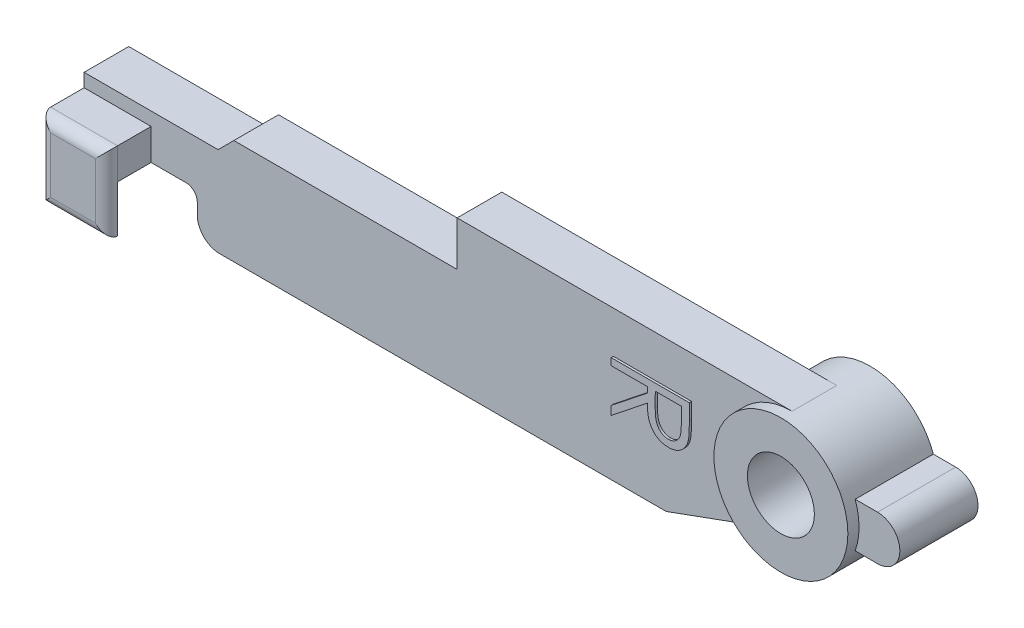
SolidWorks part; units mm, degrees
ref_plane "Piano frontale" through (0, 0, 0) normal (0, 0, 1) x (1, 0, 0)
ref_plane "Piano superiore" through (0, 0, 0) normal (0, 1, 0) x (1, 0, 0)
ref_plane "Piano destro" through (0, 0, 0) normal (1, 0, 0) x (0, 0, -1)
sketch "Schizzo1" plane through (0, 0, 0) normal (0, 0, 1) x (1, 0, 0)
  line L0 (19.0188, 0) -> (-19.0188, 0) construction
  line L1 (0, 0) -> (0, 8.6004) construction
  line L2 (-16.7071, 0.7929) -> (-10.7071, 0.7929)
  line L3 (-10.7071, 0.7929) -> (-10, 1.5)
  line L4 (-10, 1.5) -> (0, 1.5)
  line L5 (0, 1.5) -> (0, 3.5)
  line L6 (0, 3.5) -> (15, 3.5)
  line L7 (15, 3.5) -> (15, 0)
  line L8 (15, 0) -> (15, -1.155)
  line L9 (15, -1.155) -> (9.3618, -3.2071)
  line L10 (9.3618, -3.2071) -> (-11.6382, -3.2071)
  line L11 (-11.6382, -3.2071) -> (-11.6382, -1.2071)
  line L12 (-11.6382, -1.2071) -> (-16.7071, -1.2071)
  line L13 (-16.7071, -1.2071) -> (-16.7071, 0.7929)
  point P4 (0, 0)
  dimension "D1" = 15
  dimension "D2" = 10
  dimension "D3" = 6
  dimension "D4" = 1
  dimension "D5" = 2
  dimension "D6" = 6
  dimension "D7" = 20
  dimension "D8" = 21
  dimension "D9" = 3.5
  dimension "D10" = 45
  dimension "D11" = 2
  dimension "D12" = 2
extrude "Estrusione-Estrusione1" add sketch "Schizzo1" along normal blind 2
fillet "Raccordo1" radius 1 1 edges at (-11.6382, -3.2071, 1)
fillet "Raccordo2" radius 0.5 1 edges at (-11.6382, -1.2071, 1)
sketch "Schizzo2" plane through (0, 0, 0) normal (0, 0, 1) x (1, 0, 0)
  line L0 (-10.7071, 0.7929) -> (22.9117, 0.7929) construction
  line L1 (15, -1.155) -> (15, 3.5) construction
  line L2 (15, 3.5) -> (0, 3.5) construction
  circle A0 centre (15, 0.5) radius 3
  dimension "D1" = 6
extrude "Estrusione-Estrusione2" add sketch "Schizzo2" along direction (0, 0, -1) on the side of the normal blind 2.5 and the other way blind 1.5
sketch "Schizzo3" plane through (0, 0, 0) normal (0, 0, 1) x (1, 0, 0)
  line L0 (15, 0.5) -> (16.6892, 0.5) construction
  line L1 (18.8284, 1.5) -> (17.8284, 1.5)
  line L4 (18.8284, -0.5) -> (17.8284, -0.5)
  line L5 (18.8284, 1.5) -> (18.8284, 0.5) construction
  arc A1 (18.8284, -0.5) -> (18.8284, 1.5) centre (18.8284, 0.5) ccw
  circle A2 centre (15, 0.5) radius 3 construction
  arc A3 (17.8284, -0.5) -> (17.8284, 1.5) centre (15, 0.5) ccw
  dimension "D2" = 1
  dimension "D3" = 1
  dimension "D4" = 1
extrude "Estrusione-Estrusione3" add sketch "Schizzo3" along normal up to surface and the other way up to surface up to face at (-4.9758, -0.1872, 2) other way up to face at (18, 0.5, -1.5)
sketch "Schizzo4" plane through (-16.7071, 0, 0) normal (-1, 0, 0) x (0, 0, 1)
  line L0 (2, -1.2071) -> (3.5, -1.2071)
  line L1 (3.5, -1.2071) -> (3.5, -3.3071)
  line L2 (3.5, -3.3071) -> (4, -3.3071)
  line L3 (4, -3.3071) -> (4, 0.1929)
  line L4 (4, 0.1929) -> (2, 0.1929)
  line L5 (2, 0.7929) -> (2, -1.2071) construction
  line L6 (2, 0.1929) -> (2, -1.2071)
  line L9 (0, 0.7929) -> (0, -1.2071) construction
  dimension "D1" = 1.4
  dimension "D2" = 3.5
  dimension "D3" = 0.5
  dimension "D4" = 4
extrude "Estrusione-Estrusione4" add sketch "Schizzo4" against normal blind 3
fillet "Raccordo3" radius 0.5 4 edges at (-15.2071, 0.1929, 4) (-13.7071, -1.5571, 4) (-15.2071, -3.3071, 4) (-16.7071, -1.5571, 4)
sketch "Schizzo5" plane through (0, 0, 2.5) normal (0, 0, 1) x (1, 0, 0)
  circle A0 centre (15, 0.5) radius 1.5
  circle A1 centre (15, 0.5) radius 3 construction
  dimension "D1" = 1.5
extrude "Taglio-Estrusione1" cut sketch "Schizzo5" against normal through all
sketch "Schizzo6" plane through (0, 0, 2) normal (0, 0, 1) x (1, 0, 0)
  line L0 (7, 2.0786) -> (7, -1.5963) construction
  line L1 (0, 3.5) -> (0, 1.5) construction
  text T0 "R"
  dimension "D1" = 7
extrude "Estrusione-Estrusione5" add sketch "Schizzo6" along normal blind 0.1
sketch "Schizzo7" plane through (0, 0, 0) normal (0, 0, -1) x (-1, 0, 0)
  line L0 (13.7071, 0.1929) -> (16.7071, 0.1929) construction
  line L1 (16.7071, 0.1929) -> (13.7071, 0.1929) construction
  line L2 (16.7071, 0.1929) -> (16.7071, -1.2071) construction
  line L3 (16.7071, -1.2071) -> (13.7071, -1.2071) construction
  line L4 (13.7071, 0.1929) -> (13.7071, -1.2071) construction
  line L5 (16.7071, 0.1929) -> (13.7071, -1.2071) construction
  line L6 (16.7071, -1.2071) -> (13.7071, 0.1929) construction
  line L7 (13.7071, 0.1929) -> (16.7071, 0.1929)
  point P4 (15.2071, -0.5071)
ref_axis "Assi1" through (-15.2071, -0.5071, 0) along (0, 0, 1)
